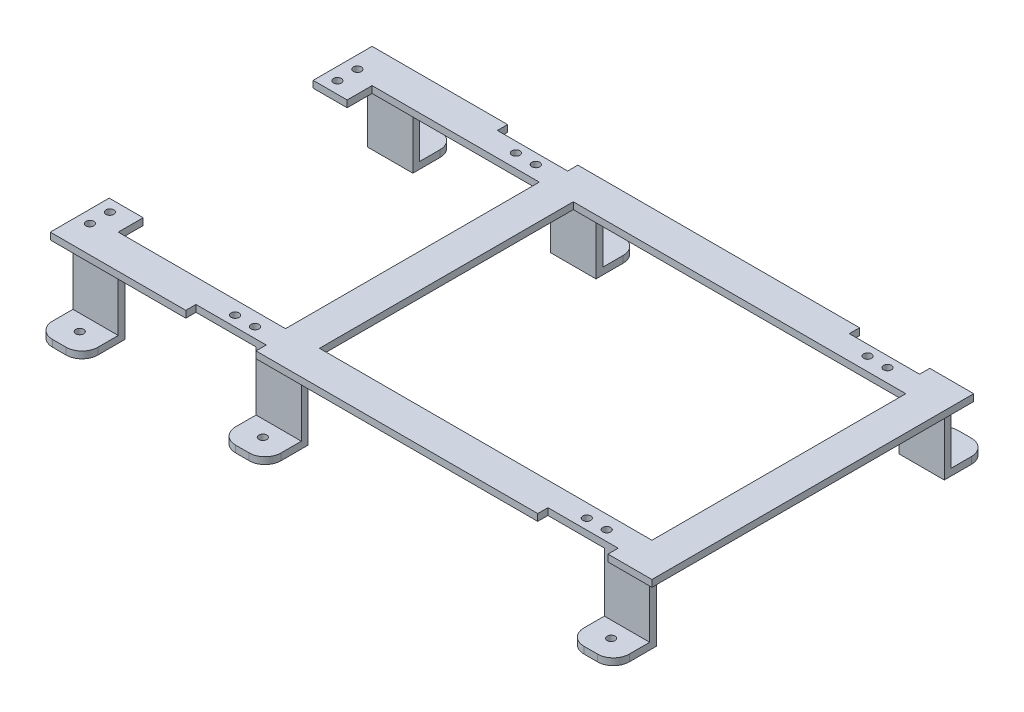
SolidWorks part; units mm, degrees
material "Acrílico (Impacto medio-alto)"
ref_plane "Alzado" through (0, 0, 0) normal (0, 0, 1) x (1, 0, 0)
ref_plane "Planta" through (0, 0, 0) normal (0, 1, 0) x (1, 0, 0)
ref_plane "Vista lateral" through (0, 0, 0) normal (1, 0, 0) x (0, 0, -1)
sketch "Croquis1" plane through (0, 0, 0) normal (0, 1, 0) x (1, 0, 0)
  line L0 (117.75, 56) -> (-117.75, 56)
  line L1 (132.75, -71) -> (-132.75, -71)
  line L2 (132.75, -71) -> (132.75, 71)
  line L3 (132.75, 71) -> (-132.75, 71)
  line L4 (-132.75, -71) -> (-132.75, 71)
  line L5 (132.75, -71) -> (-132.75, 71) construction
  line L6 (132.75, 71) -> (-132.75, -71) construction
  line L7 (-117.75, -56) -> (-117.75, 56)
  line L8 (117.75, -56) -> (-117.75, -56)
  line L9 (117.75, -56) -> (117.75, 56)
  point P0 (0, 0)
  dimension "D1" = 142
  dimension "D2" = 265.5
  dimension "D3" = 15
extrude "Saliente-Extruir1" add sketch "Croquis1" along normal blind 3
ref_plane "Plano1" through (-127.25, 0, 0) normal (1, 0, 0) x (0, 0, -1)
sketch "Croquis2" plane through (-127.25, 0, 0) normal (-1, 0, 0) x (0, 0, 1)
  line L0 (66.5, 0) -> (66.5, -26)
  line L6 (63.5, 0) -> (66.5, 0)
  line L8 (82.5, -29) -> (82.5, -26)
  line L9 (82.5, -26) -> (66.5, -26)
  line L20 (63.5, 0) -> (63.5, -29)
  line L21 (63.5, -29) -> (82.5, -29)
  line L22 (71, 3) -> (71, 0) construction
  line L23 (-71, 0) -> (71, 0) construction
  dimension "D1" = 29
  dimension "D2" = 3
  dimension "D3" = 4.5
  dimension "D4" = 19
  dimension "D5" = 3
extrude "Saliente-Extruir2" add sketch "Croquis2" against normal blind 20
mirror "Simetría1" about plane through (0, 0, 0) normal (1, 0, 0) of "Saliente-Extruir2"
mirror "Simetría2" about plane through (0, 0, 0) normal (0, 0, 1) of "Simetría1"
sketch "Croquis3" plane through (0, 3, 0) normal (0, 1, 0) x (1, 0, 0)
  line L1 (-120, 32.5) -> (-60, 32.5)
  line L2 (-120, 32.5) -> (-120, -32.5)
  line L3 (-120, -32.5) -> (-60, -32.5)
  line L4 (-60, 32.5) -> (-60, -32.5)
  point P4 (-60, 0)
  dimension "D1" = 65
  dimension "D2" = 60
  dimension "D3" = 60
extrude "Cortar-Extruir1" [suppressed] cut sketch "Croquis3" against normal through all
mirror "Simetría3" [suppressed] about plane through (0, 0, 0) normal (1, 0, 0)
ref_plane "Plano2" through (-36.45, 0, 0) normal (1, 0, 0) x (0, 0, -1)
sketch "Croquis4" plane through (-36.45, 0, 0) normal (1, 0, 0) x (0, 0, -1)
  line L12 (-63.5, 0) -> (-66.5, 0)
  line L13 (-66.5, 0) -> (-66.5, -26)
  line L14 (-66.5, -26) -> (-82.5, -26)
  line L15 (-82.5, -26) -> (-82.5, -29)
  line L16 (-82.5, -29) -> (-63.5, -29)
  line L17 (-82.5, -29) -> (-63.5, -29)
  line L19 (-66.5, 0) -> (-66.5, -26)
  line L20 (-66.5, -26) -> (-82.5, -26)
  line L21 (-82.5, -26) -> (-82.5, -29)
  line L28 (-63.5, 0) -> (-66.5, 0)
  line L38 (-63.5, -29) -> (-63.5, 0)
  line L40 (-63.5, -29) -> (-63.5, 0)
  dimension "D1" = 0
extrude "Saliente-Extruir3" add sketch "Croquis4" along normal mid plane 20
mirror "Simetría4" about plane through (0, 0, 0) normal (0, 0, 1) of "Saliente-Extruir3"
sketch "Croquis5" plane through (0, 3, 0) normal (0, 1, 0) x (1, 0, 0)
  line L1 (-105.499, -45) -> (-143.7054, -45)
  line L2 (-105.499, -45) -> (-105.499, 45)
  line L3 (-105.499, 45) -> (-143.7054, 45)
  line L4 (-143.7054, -45) -> (-143.7054, 45)
  line L5 (-105.499, -45) -> (-143.7054, 45) construction
  line L6 (-105.499, 45) -> (-143.7054, -45) construction
  point P0 (-124.6022, 0)
  dimension "D1" = 90
extrude "Cortar-Extruir2" cut sketch "Croquis5" against normal through all
sketch "Croquis7" plane through (0, 3, 0) normal (0, 1, 0) x (1, 0, 0)
  line L1 (-49.2, 56) -> (-23.2245, 56)
  line L2 (-49.2, 56) -> (-49.2, -56)
  line L3 (-49.2, -56) -> (-23.2245, -56)
  line L4 (-23.2245, 56) -> (-23.2245, -56)
extrude "Cortar-Extruir3" [suppressed] cut sketch "Croquis7" against normal through all
sketch "Croquis6" plane through (0, 3, 0) normal (0, 1, 0) x (1, 0, 0)
  line L0 (-36.45, 56) -> (-36.45, -56) construction
  line L1 (117.75, 56) -> (-117.75, 56) construction
  line L2 (-117.75, -56) -> (117.75, -56) construction
  line L4 (-132.75, 71) -> (-132.75, 45) construction
  line L6 (-43.95, 56) -> (-28.95, 56)
  line L7 (-43.95, 56) -> (-43.95, -56)
  line L8 (-43.95, -56) -> (-28.95, -56)
  line L9 (-28.95, 56) -> (-28.95, -56)
  point P12 (-36.45, 56)
  point P13 (-36.45, -56)
  dimension "D1" = 96.3
  dimension "D2" = 15
extrude "Saliente-Extruir4" add sketch "Croquis6" against normal up to surface (3 mm away) up to face at (-36.45, 0, -65)
sketch "Croquis8" plane through (0, 3, 0) normal (0, 1, 0) x (1, 0, 0)
  line L0 (132.75, 71) -> (-132.75, 71) construction
  line L1 (113.35, 66.5) -> (82.35, 66.5)
  line L2 (113.35, 66.5) -> (113.35, 71)
  line L3 (113.35, 71) -> (82.35, 71)
  line L4 (82.35, 66.5) -> (82.35, 71)
  line L5 (132.75, -71) -> (132.75, 71) construction
  line L6 (-132.75, 71) -> (-132.75, 45) construction
  line L7 (-41.95, 66.5) -> (-72.95, 66.5)
  line L8 (-41.95, 66.5) -> (-41.95, 71)
  line L9 (-41.95, 71) -> (-72.95, 71)
  line L10 (-72.95, 66.5) -> (-72.95, 71)
  dimension "D1" = 4.5
  dimension "D2" = 19.4
  dimension "D3" = 31
  dimension "D4" = 59.8
extrude "Cortar-Extruir4" cut sketch "Croquis8" against normal up to surface (3 mm away) up to face at (-68.7, 0, 0)
sketch "Croquis9" plane through (0, 3, 0) normal (0, 1, 0) x (1, 0, 0)
  circle A0 centre (-127.25, 59) radius 1.75
  circle A1 centre (-127.25, 50.2) radius 1.75
extrude "Cortar-Extruir5" cut sketch "Croquis9" against normal through all
sketch "Croquis11" plane through (0, 3, 0) normal (0, 1, 0) x (1, 0, 0)
  circle A0 centre (103.7509, 61.953) radius 1.75
  circle A1 centre (94.9509, 61.953) radius 1.75
extrude "Cortar-Extruir7" cut sketch "Croquis11" against normal blind 4
sketch "Croquis12" plane through (0, 3, 0) normal (0, 1, 0) x (1, 0, 0)
  circle A0 centre (-51.4491, 61.953) radius 1.75
  circle A1 centre (-60.2491, 61.953) radius 1.75
  dimension "D1" = 3.5
extrude "Cortar-Extruir8" cut sketch "Croquis12" against normal blind 4
mirror "Simetría5" about plane through (0, 0, 0) normal (0, 0, 1) of "Cortar-Extruir8", "Cortar-Extruir7", "Cortar-Extruir5"
mirror "Simetría6" about plane through (0, 0, 0) normal (0, 0, 1) of "Cortar-Extruir4"
fillet "Redondeo1" radius 7 2 edges at (-127.25, -27.5, 82.5) (-107.25, -27.5, 82.5)
fillet "Redondeo2" radius 7 4 edges at (-26.45, -27.5, 82.5) (-46.45, -27.5, 82.5) (127.25, -27.5, 82.5) (107.25, -27.5, 82.5)
sketch "Croquis13" plane through (0, -26, 0) normal (0, 1, 0) x (1, 0, 0)
  line L0 (-114.25, -82.5) -> (-120.25, -82.5) construction
  line L1 (-127.25, -75.5) -> (-127.25, -66.5) construction
  circle A0 centre (-117.25, -73.5) radius 1.75
  dimension "D2" = 3.5
  dimension "D1" = 9
  dimension "D3" = 10
extrude "Cortar-Extruir9" cut sketch "Croquis13" against normal through all
mirror "Simetría7" about plane through (0, 0, 0) normal (1, 0, 0) of "Cortar-Extruir9"
sketch "Croquis15" plane through (0, -26, 0) normal (0, 1, 0) x (1, 0, 0)
  line L0 (-46.45, -66.5) -> (-46.45, -75.5) construction
  line L1 (-33.45, -82.5) -> (-39.45, -82.5) construction
  circle A0 centre (-36.45, -73.5) radius 1.75
  dimension "D3" = 3.5
  dimension "D1" = 10
  dimension "D2" = 9
extrude "Cortar-Extruir10" cut sketch "Croquis15" against normal through all
mirror "Simetría12" about plane through (0, 0, 0) normal (0, 0, 1) of "Cortar-Extruir10", "Simetría7", "Cortar-Extruir9"
fillet "Redondeo3" radius 7 6 edges at (-127.25, -27.5, -82.5) (-107.25, -27.5, -82.5) (-46.45, -27.5, -82.5) (-26.45, -27.5, -82.5) (107.25, -27.5, -82.5) (127.25, -27.5, -82.5)
